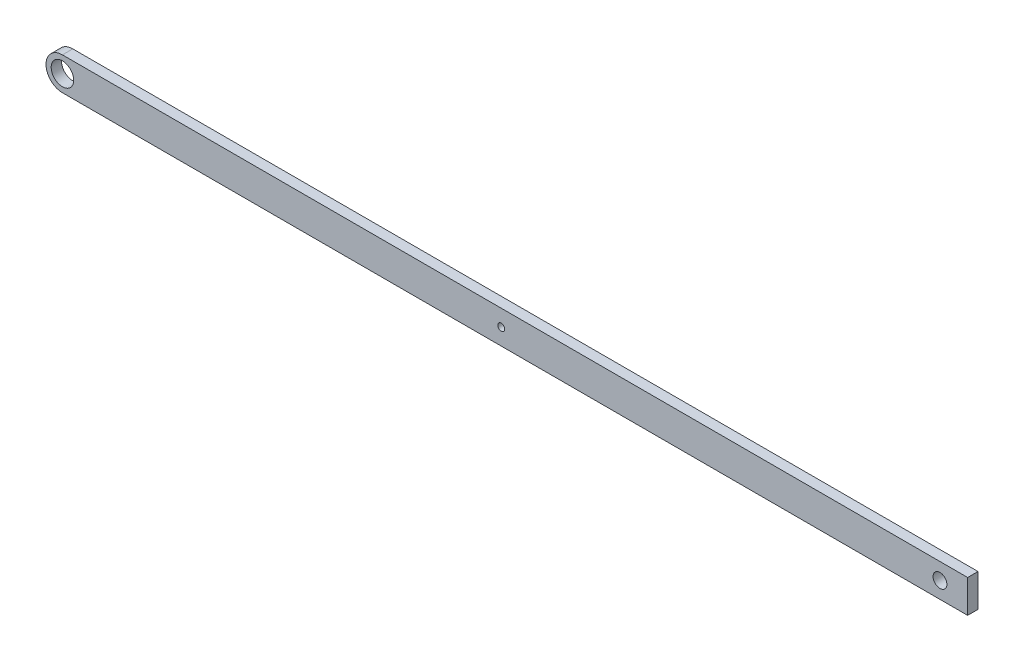
SolidWorks part; units mm, degrees
material "Gray Cast Iron"
ref_plane "Front Plane" through (0, 0, 0) normal (0, 0, 1) x (1, 0, 0)
ref_plane "Top Plane" through (0, 0, 0) normal (0, 1, 0) x (1, 0, 0)
ref_plane "Right Plane" through (0, 0, 0) normal (1, 0, 0) x (0, 0, -1)
sketch "Sketch1" plane through (0, 0, 0) normal (0, 0, 1) x (1, 0, 0)
  line L0 (0, -4.75) -> (262, -4.75)
  line L1 (262, -4.75) -> (262, 4.75)
  line L2 (262, 4.75) -> (0, 4.75)
  arc A0 (0, 4.75) -> (0, -4.75) centre (0, 0) ccw
extrude "Boss-Extrude1" add sketch "Sketch1" along normal mid plane 3
sketch "Sketch2" plane through (0, 0, 0) normal (0, 0, 1) x (1, 0, 0)
  circle A0 centre (0, 0) radius 3.25
  circle A1 centre (127, 0) radius 1
  circle A2 centre (254, 0) radius 2
  dimension "D1" = 6.5
  dimension "D2" = 2
  dimension "D3" = 4
extrude "Cut-Extrude1" cut sketch "Sketch2" against normal mid plane 40
